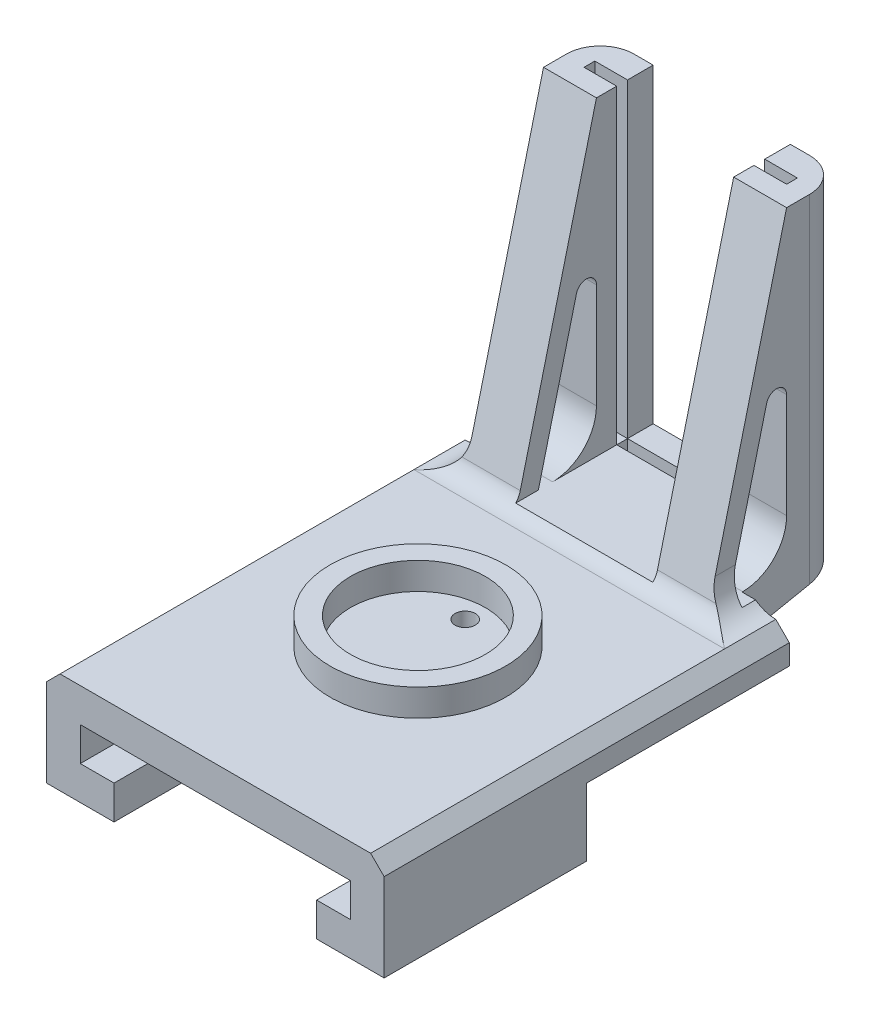
SolidWorks part; units mm, degrees
material "9400A光敏树脂"
ref_plane "前视基准面" through (0, 0, 0) normal (0, 0, 1) x (1, 0, 0)
ref_plane "上视基准面" through (0, 0, 0) normal (0, 1, 0) x (1, 0, 0)
ref_plane "右视基准面" through (0, 0, 0) normal (1, 0, 0) x (0, 0, -1)
other "Configuration Table"
sketch "草图2" plane through (0, 0, 0) normal (0, 1, 0) x (1, 0, 0)
  line L1 (-30, 30) -> (30, 30)
  line L2 (-30, 30) -> (-30, -30)
  line L3 (-30, -30) -> (30, -30)
  line L4 (30, 30) -> (30, -30)
  line L5 (-30, 30) -> (30, -30) construction
  line L6 (-30, -30) -> (30, 30) construction
  point P0 (0, 0)
  dimension "D1" = 60
  dimension "D2" = 60
extrude "凸台-拉伸1" add sketch "草图2" along normal blind 3
sketch "草图7" plane through (0, 0, 0) normal (0, 0, 1) x (1, 0, 0)
  line L0 (0, -1000) -> (0, 49000) construction
  line L1 (-25, 0) -> (-25, -10)
  line L2 (-30, 0) -> (30, 0) construction
  line L3 (-25, -10) -> (-15, -10)
  line L4 (-15, -10) -> (-15, -5)
  line L5 (-15, -5) -> (-20, -5)
  line L6 (-20, -5) -> (-20, 0)
  line L7 (-20, 0) -> (-25, 0)
  line L8 (-30, 3) -> (-30, 0) construction
  line L9 (20, 0) -> (25, 0)
  line L10 (20, -5) -> (20, 0)
  line L11 (15, -5) -> (20, -5)
  line L12 (15, -10) -> (15, -5)
  line L13 (25, -10) -> (15, -10)
  line L14 (25, 0) -> (25, -10)
  dimension "D1" = 5
  dimension "D2" = 5
  dimension "D3" = 10
  dimension "D4" = 5
  dimension "D5" = 5
extrude "凸台-拉伸3" add sketch "草图7" against normal blind 30 from surface at 30 starting at face at (0, 1.5, 30)
sketch "草图8" plane through (0, 0, 0) normal (0, 1, 0) x (1, 0, 0)
  line L0 (0, -1000) -> (0, 49000) construction
  line L1 (-18, 25) -> (18, 25)
  line L2 (18, 25) -> (18, 45)
  line L3 (18, 45) -> (-18, 45)
  line L4 (-18, 45) -> (-18, 25)
  line L5 (30, 30) -> (-30, 30) construction
  point P7 (0, 25)
  dimension "D1" = 36
  dimension "D2" = 20
  dimension "D3" = 5
extrude "凸台-拉伸4" add sketch "草图8" along normal blind 3 from surface at 3 starting at face at (0, 3, 0)
sketch "草图10" plane through (0, 0, 0) normal (0, 1, 0) x (1, 0, 0)
  line L0 (-18, 45) -> (18, 45) construction
  line L1 (-10.16, 41.2) -> (10.16, 41.2)
  line L2 (-10.16, 41.2) -> (-10.16, 39.6)
  line L3 (-10.16, 39.6) -> (10.16, 39.6)
  line L4 (10.16, 41.2) -> (10.16, 39.6)
  point P6 (0, 45)
  point P7 (0, 41.2)
  dimension "D1" = 3.8
  dimension "D2" = 1.6
  dimension "D3" = 20.32
extrude "切除-拉伸2" cut sketch "草图10" against normal up to surface (3 mm away) from surface at 6 up to face at (0, 3, -37.5) starting at face at (0, 6, -35)
sketch "草图11" plane through (0, 0, 0) normal (0, 1, 0) x (1, 0, 0)
  line L0 (0, -1000) -> (0, 49000) construction
  line L1 (18, 41.2) -> (15, 41.2) construction
  line L2 (18, 45) -> (18, 25) construction
  line L3 (10.16, 41.2) -> (-10.16, 41.2) construction
  line L4 (10.16, 41.2) -> (10.16, 45)
  line L5 (-18, 45) -> (18, 45) construction
  line L6 (10.16, 45) -> (18, 45)
  line L7 (15, 39.6) -> (18, 39.6) construction
  line L8 (-10.16, 39.6) -> (10.16, 39.6) construction
  line L9 (18, 45) -> (18, 36.6)
  line L10 (18, 36.6) -> (10.16, 36.6)
  line L11 (10.16, 36.6) -> (10.16, 39.6)
  line L12 (10.16, 39.6) -> (15, 39.6)
  line L13 (10.16, 41.2) -> (15, 41.2)
  line L14 (15, 41.2) -> (15, 39.6)
  line L15 (-15, 39.6) -> (-18, 39.6) construction
  line L16 (-18, 41.2) -> (-15, 41.2) construction
  line L17 (-15, 41.2) -> (-15, 39.6)
  line L18 (-10.16, 41.2) -> (-15, 41.2)
  line L19 (-10.16, 39.6) -> (-15, 39.6)
  line L20 (-10.16, 36.6) -> (-10.16, 39.6)
  line L21 (-18, 36.6) -> (-10.16, 36.6)
  line L22 (-18, 45) -> (-18, 36.6)
  line L23 (-10.16, 45) -> (-18, 45)
  line L24 (-10.16, 41.2) -> (-10.16, 45)
  dimension "D1" = 3
  dimension "D2" = 3
  dimension "D3" = 3
extrude "凸台-拉伸5" add sketch "草图11" along normal blind 46 from surface at 6 starting at face at (0, 6, -40.4)
sketch "草图12" plane through (0, 0, 0) normal (1, 0, 0) x (0, 0, -1)
  line L0 (30, 0) -> (35, 3)
  line L1 (45, 3) -> (30, 3) construction
  line L2 (35, 3) -> (30, 3)
  line L3 (30, 3) -> (30, 0) construction
  line L4 (30, 3) -> (30, 0)
  dimension "D1" = 5
extrude "凸台-拉伸6" add sketch "草图12" along normal up to surface (36 mm away) from surface at -18 up to face at (18, 17.8571, -34.7429) starting at face at (-18, 17.8571, -34.7429)
sketch "草图13" plane through (0, 0, 0) normal (1, 0, 0) x (0, 0, -1)
  line L0 (25, 6) -> (36.6, 52)
  line L1 (25, 6) -> (28, 6)
  line L2 (36.6, 40.1034) -> (36.6, 52)
  line L3 (28, 6) -> (36.6, 40.1034)
  dimension "D1" = 3
extrude "凸台-拉伸8" add sketch "草图13" against normal up to surface (7.84 mm away) from surface at 18 up to face at (10.16, 29, -43.1) starting at face at (18, 14.2222, -34.2444)
sketch "草图14" plane through (0, 0, 0) normal (1, 0, 0) x (0, 0, -1)
  line L4 (36.6, 52) -> (25, 6)
  line L5 (36.6, 40.1034) -> (36.6, 52)
  line L6 (28, 6) -> (36.6, 40.1034)
  line L7 (25, 6) -> (28, 6)
  line L8 (36.6, 52) -> (25, 6)
  line L9 (36.6, 40.1034) -> (36.6, 52)
  line L10 (28, 6) -> (36.6, 40.1034)
  line L11 (25, 6) -> (28, 6)
  dimension "D1" = 0
extrude "凸台-拉伸9" add sketch "草图14" against normal up to surface (7.84 mm away) from surface at -10.16 up to face at (-18, 14.2222, -34.2444) starting at face at (-10.16, 29, -43.1)
sketch "草图15" plane through (0, 0, 0) normal (1, 0, 0) x (0, 0, -1)
  line L0 (25, 3) -> (24.2435, 3)
  line L1 (-30, 3) -> (30, 3) construction
  line L2 (24.2435, 3) -> (25, 6)
  line L3 (25, 6) -> (25, 3)
  line L4 (25, 6) -> (36.6, 52) construction
extrude "凸台-拉伸10" add sketch "草图15" against normal up to surface (36 mm away) from surface
sketch "草图16" plane through (0, 0, 0) normal (0, 1, 0) x (1, 0, 0)
  line L1 (25, -30) -> (30, -30)
  line L2 (25, -30) -> (25, 30)
  line L3 (25, 30) -> (30, 30)
  line L4 (30, -30) -> (30, 30)
  line L5 (-25, -30) -> (-30, -30)
  line L6 (-25, -30) -> (-25, 30)
  line L7 (-25, 30) -> (-30, 30)
  line L8 (-30, -30) -> (-30, 30)
extrude "切除-拉伸3" cut sketch "草图16" along normal up to surface (3 mm away) from surface at 0 up to face at (0, 3, -13.5609) starting at face at (0, 0, 4.2857)
sketch "草图17" plane through (0, 0, 0) normal (1, 0, 0) x (0, 0, -1)
  line L0 (30, 0) -> (45, 3)
  line L1 (45, 3) -> (30, 3)
  line L2 (30, 3) -> (30, 0)
extrude "凸台-拉伸11" add sketch "草图17" against normal blind 4 from surface at 18 starting at face at (18, 16.5714, -35.1205)
sketch "草图18" plane through (0, 0, 0) normal (1, 0, 0) x (0, 0, -1)
  line L0 (30, 0) -> (30, 3)
  line L1 (30, 3) -> (45, 3)
  line L2 (45, 3) -> (30, 0)
extrude "凸台-拉伸12" add sketch "草图18" along normal blind 4 from surface at -18 starting at face at (-18, 17.3678, -33.7333)
fillet "圆角3" radius 5 2 edges at (-18, 27.5, -45) (18, 27.5, -45)
fillet "圆角4" radius 10 1 edges at (0, 3, -35)
sketch "草图22" plane through (0, 0, 0) normal (0, 0, 1) x (1, 0, 0)
  line L1 (25, 3) -> (-25, 3)
  line L2 (25, 3) -> (25, 5)
  line L3 (25, 5) -> (-25, 5)
  line L4 (-25, 3) -> (-25, 5)
  dimension "D1" = 50
  dimension "D2" = 2
extrude "凸台-拉伸14" add sketch "草图22" against normal up to surface (60 mm away) from surface at 30 up to face at (-21.5, 1.5, -30) starting at face at (0, -4.5, 30)
sketch "草图24" plane through (0, 0, 0) normal (0, 0, 1) x (1, 0, 0)
  line L0 (-25, 5) -> (-23, 5)
  line L1 (25, 5) -> (-25, 5) construction
  line L2 (-23, 5) -> (-25, 3)
  line L3 (-25, 5) -> (-25, -10) construction
  line L4 (-25, 3) -> (-25, 5)
  line L5 (25, 5) -> (25, 3)
  line L6 (25, -10) -> (25, 5) construction
  line L7 (25, 3) -> (23, 5)
  line L8 (23, 5) -> (25, 5)
  dimension "D1" = 2
  dimension "D2" = 2
  dimension "D3" = 2
  dimension "D4" = 2
extrude "切除-拉伸4" cut sketch "草图24" against normal up to surface (60 mm away) from surface at 30 up to face at (-21.5, 2.5, -30) starting at face at (0, -4.1667, 30)
sketch "草图26" plane through (0, 0, 0) normal (0, 1, 0) x (1, 0, 0)
  circle A0 centre (0, 0) radius 12.5
  dimension "D1" = 25
extrude "切除-拉伸6" cut sketch "草图26" along normal blind 2 from surface at 0 starting at face at (0, 0, -10)
fillet "圆角5" radius 3 1 edges at (0, 0, 12.5)
fillet "圆角7" radius 5 2 edges at (-18, 5, -27.3739) (18, 5, -27.3739)
fillet "圆角8" radius 6.5 2 edges at (14.08, 6, -36.6) (-14.08, 6, -36.6)
fillet "圆角9" radius 1.5 2 edges at (-14.08, 40.1034, -36.6) (14.08, 40.1034, -36.6)
fillet "圆角10" radius 3 1 edges at (0, 5, -24.7478)
sketch "草图27" plane through (0, 0, 0) normal (0, 1, 0) x (1, 0, 0)
  line L0 (0, -7) -> (0, 7) construction
  circle A0 centre (0, 7) radius 1.5
  circle A1 centre (0, -7) radius 1.5
  point P4 (0, 0)
  dimension "D2" = 3
  dimension "D3" = 3
  dimension "D1" = 14
extrude "切除-拉伸7" cut sketch "草图27" against normal up to surface (3 mm away) from surface at 5 up to face at (0, 2, 12.5) starting at face at (0, 5, 3.7948)
sketch "草图28" plane through (0, 0, 0) normal (0, 1, 0) x (1, 0, 0)
  circle A0 centre (0, 0) radius 10
  circle A1 centre (0, 0) radius 13
  dimension "D1" = 20
  dimension "D2" = 26
extrude "凸台-拉伸15" add sketch "草图28" along normal blind 4 from surface at 5 starting at face at (-1.5, 5, -7)
